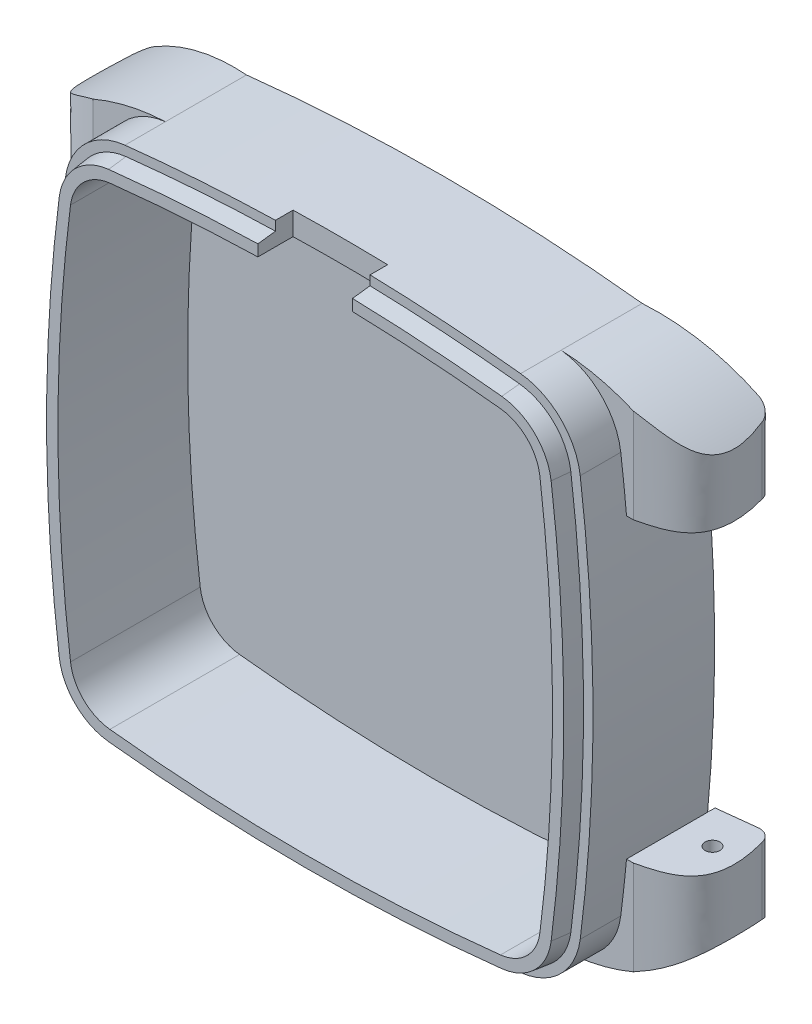
SolidWorks part; units mm, degrees
material "Özel Plastik"
ref_plane "Ön Düzlem" through (0, 0, 0) normal (0, 0, 1) x (1, 0, 0)
ref_plane "Üst Düzlem" through (0, 0, 0) normal (0, 1, 0) x (1, 0, 0)
ref_plane "Sağ Düzlem" through (0, 0, 0) normal (1, 0, 0) x (0, 0, -1)
sketch "Çizim1" plane through (0, 0, 0) normal (0, 0, 1) x (1, 0, 0)
  line L1 (-20, -20) -> (20, -20)
  line L2 (-20, -20) -> (-20, 20)
  line L3 (-20, 20) -> (20, 20)
  line L4 (20, -20) -> (20, 20)
  line L5 (-20, -20) -> (20, 20) construction
  line L6 (-20, 20) -> (20, -20) construction
  point P0 (0, 0)
  dimension "D1" = 40
  dimension "D2" = 40
extrude "Yükseklik-Ekstrüzyon1" add sketch "Çizim1" along normal mid plane 9 contours L3 L4 L1 L2
sketch "Çizim2" plane through (0, 0, 4.5) normal (0, 0, 1) x (1, 0, 0)
  line L0 (-20, 18.5) -> (20, 18.5) construction
  line L1 (-20, -20) -> (-20, 20) construction
  line L2 (20, -20) -> (20, 20) construction
  line L3 (-20, 20) -> (20, 20) construction
  line L4 (0, 0) -> (12.6557, 0) construction
  line L5 (-20, 20) -> (20, 20)
  line L6 (20, 20) -> (20, 18.5)
  line L7 (-20, 20) -> (-20, 18.5)
  line L8 (-20, -18.5) -> (20, -18.5) construction
  line L9 (-20, -20) -> (-20, -18.5)
  line L10 (20, -20) -> (20, -18.5)
  line L11 (-20, -20) -> (20, -20)
  arc A0 (-20, 18.5) -> (20, 18.5) centre (0, -114.0833) cw
  arc A1 (-20, -18.5) -> (20, -18.5) centre (0, 114.0833) ccw
  line M4 (-20, 20) -> (-20, -20)
  line M5 (-20, -20) -> (20, -20)
  line M6 (20, -20) -> (20, 20)
  line M7 (20, 20) -> (-20, 20)
  dimension "D1" = 1.5
extrude "Kes-Ekstrüzyon1" cut sketch "Çizim2" against normal through all contours A0 M7 M6 | A0 L5 M4 | A1 M4 M5 | A1 L11 M6 region at (-15.0056, 19.5504, 4.5) region at (15.0056, 19.5504, 4.5) region at (-15.0056, -19.5504, 4.5) region at (15.0056, -19.5504, 4.5)
sketch "Çizim3" plane through (0, 0, 4.5) normal (0, 0, 1) x (1, 0, 0)
  line L0 (18.5, 18.7176) -> (18.5, -18.7176) construction
  line L1 (20, -18.5) -> (20, 18.5) construction
  line L2 (20, 18.5) -> (20, -18.5)
  line L3 (0, 0) -> (0, -12.7146) construction
  line L4 (-18.5, 18.7176) -> (-18.5, -18.7176) construction
  line L5 (-20, 18.5) -> (-20, -18.5)
  arc A0 (20, 18.5) -> (-20, 18.5) centre (0, -114.0833) ccw construction
  arc A1 (-20, -18.5) -> (20, -18.5) centre (0, 114.0833) ccw construction
  arc A2 (18.5, 18.7176) -> (18.5, -18.7176) centre (-97.533, 0) cw
  arc A3 (18.5, -18.7176) -> (20, -18.5) centre (0, 114.0833) ccw
  arc A4 (20, 18.5) -> (18.5, 18.7176) centre (0, -114.0833) ccw
  arc A5 (-20, 18.5) -> (-18.5, 18.7176) centre (0, -114.0833) cw
  arc A6 (-18.5, -18.7176) -> (-20, -18.5) centre (0, 114.0833) cw
  arc A7 (-18.5, 18.7176) -> (-18.5, -18.7176) centre (97.533, 0) ccw
  arc M3 (-20, -18.5) -> (20, -18.5) centre (0, 114.0833) ccw
  line M4 (20, -18.5) -> (20, 18.5)
  arc M5 (20, 18.5) -> (-20, 18.5) centre (0, -114.0833) ccw
  line M6 (-20, 18.5) -> (-20, -18.5)
  dimension "D1" = 1.5
extrude "Kes-Ekstrüzyon2" cut sketch "Çizim3" against normal through all contours A2 L2 M5 | A2 M4 M3 | A7 L5 M3 | A7 M5 M6 region at (19.5513, 13.9634, 4.5) region at (19.5513, -13.9634, 4.5) region at (-19.5513, 13.9634, 4.5) region at (-19.5513, -13.9634, 4.5)
fillet "Radyus1" radius 5 4 edges at (-18.5, -18.7176, 0) (18.5, -18.7176, 0) (-18.5, 18.7176, 0) (18.5, 18.7176, 0)
shell "İç Boşaltma1" thickness 0.7 removed face at (0, 0, 4.5)
sketch "Çizim4" plane through (0, 0, -3.8) normal (0, 0, 1) x (1, 0, 0)
  arc A16 (-14.4573, -17.5082) -> (14.4573, -17.5082) centre (0, 114.0833) ccw
  arc A17 (14.4573, -17.5082) -> (17.3704, -14.6452) centre (14.0969, -14.2279) ccw
  arc A18 (17.3704, -14.6452) -> (17.3704, 14.6452) centre (-97.533, 0) ccw
  arc A19 (17.3704, 14.6452) -> (14.4573, 17.5082) centre (14.0969, 14.2279) ccw
  arc A20 (14.4573, 17.5082) -> (-14.4573, 17.5082) centre (0, -114.0833) ccw
  arc A21 (-14.4573, 17.5082) -> (-17.3704, 14.6452) centre (-14.0969, 14.2279) ccw
  arc A22 (-17.3704, 14.6452) -> (-17.3704, -14.6452) centre (97.533, 0) ccw
  arc A23 (-17.3704, -14.6452) -> (-14.4573, -17.5082) centre (-14.0969, -14.2279) ccw
  arc A24 (-14.4573, -17.5082) -> (14.4573, -17.5082) centre (0, 114.0833) ccw
  arc A25 (14.4573, -17.5082) -> (17.3704, -14.6452) centre (14.0969, -14.2279) ccw
  arc A26 (17.3704, -14.6452) -> (17.3704, 14.6452) centre (-97.533, 0) ccw
  arc A27 (17.3704, 14.6452) -> (14.4573, 17.5082) centre (14.0969, 14.2279) ccw
  arc A28 (14.4573, 17.5082) -> (-14.4573, 17.5082) centre (0, -114.0833) ccw
  arc A29 (-14.4573, 17.5082) -> (-17.3704, 14.6452) centre (-14.0969, 14.2279) ccw
  arc A30 (-17.3704, 14.6452) -> (-17.3704, -14.6452) centre (97.533, 0) ccw
  arc A31 (-17.3704, -14.6452) -> (-14.4573, -17.5082) centre (-14.0969, -14.2279) ccw
  arc A32 (-14.5665, -18.5022) -> (14.5665, -18.5022) centre (0, 114.0833) ccw
  arc A33 (14.5665, -18.5022) -> (18.3624, -14.7716) centre (14.0969, -14.2279) ccw
  arc A34 (18.3624, -14.7716) -> (18.3624, 14.7716) centre (-97.533, 0) ccw
  arc A35 (18.3624, 14.7716) -> (14.5665, 18.5022) centre (14.0969, 14.2279) ccw
  arc A36 (14.5665, 18.5022) -> (-14.5665, 18.5022) centre (0, -114.0833) ccw
  arc A37 (-14.5665, 18.5022) -> (-18.3624, 14.7716) centre (-14.0969, 14.2279) ccw
  arc A38 (-18.3624, 14.7716) -> (-18.3624, -14.7716) centre (97.533, 0) ccw
  arc A39 (-18.3624, -14.7716) -> (-14.5665, -18.5022) centre (-14.0969, -14.2279) ccw
  arc A40 (-14.5665, -18.5022) -> (14.5665, -18.5022) centre (0, 114.0833) ccw
  arc A41 (14.5665, -18.5022) -> (18.3624, -14.7716) centre (14.0969, -14.2279) ccw
  arc A42 (18.3624, -14.7716) -> (18.3624, 14.7716) centre (-97.533, 0) ccw
  arc A43 (18.3624, 14.7716) -> (14.5665, 18.5022) centre (14.0969, 14.2279) ccw
  arc A44 (14.5665, 18.5022) -> (-14.5665, 18.5022) centre (0, -114.0833) ccw
  arc A45 (-14.5665, 18.5022) -> (-18.3624, 14.7716) centre (-14.0969, 14.2279) ccw
  arc A46 (-18.3624, 14.7716) -> (-18.3624, -14.7716) centre (97.533, 0) ccw
  arc A47 (-18.3624, -14.7716) -> (-14.5665, -18.5022) centre (-14.0969, -14.2279) ccw
  dimension "D2" = 0
  dimension "D1" = 1
extrude "Yükseklik-Ekstrüzyon2" add sketch "Çizim4" along normal blind 9.6
sketch "Çizim7" plane through (0, 0, -4.5) normal (0, 0, -1) x (-1, 0, 0)
  line L0 (25.5, 14) -> (25.5, -14)
  line L1 (0, 0) -> (0, 12.7906) construction
  line L2 (0, 0) -> (-9.1265, 0) construction
  line L3 (-25.5, 14) -> (-25.5, -14)
  arc A0 (14.643, -19.198) -> (19.0568, -14.8601) centre (14.0969, -14.2279) ccw construction
  arc A1 (19.0568, -14.8601) -> (19.0568, 14.8601) centre (-97.533, 0) ccw construction
  arc A2 (19.0568, 14.8601) -> (14.643, 19.198) centre (14.0969, 14.2279) ccw construction
  arc A3 (14.643, -19.198) -> (19.0568, -14.8601) centre (14.0969, -14.2279) ccw
  arc A4 (19.0568, -14.8601) -> (19.0568, 14.8601) centre (-97.533, 0) ccw
  arc A5 (19.0568, 14.8601) -> (14.643, 19.198) centre (14.0969, 14.2279) ccw
  arc A6 (14.643, -19.198) -> (25.5, -14) centre (13.9336, -3.779) ccw
  arc A7 (14.643, 19.198) -> (25.5, 14) centre (13.9336, 3.779) cw
  arc A8 (-14.643, 19.198) -> (-25.5, 14) centre (-13.9336, 3.779) ccw
  arc A9 (-14.643, -19.198) -> (-25.5, -14) centre (-13.9336, -3.779) cw
  arc A10 (-19.0568, 14.8601) -> (-14.643, 19.198) centre (-14.0969, 14.2279) cw
  arc A11 (-19.0568, -14.8601) -> (-19.0568, 14.8601) centre (97.533, 0) cw
  arc A12 (-14.643, -19.198) -> (-19.0568, -14.8601) centre (-14.0969, -14.2279) cw
  point P5 (20, 0)
  dimension "D1" = 5.5
  dimension "D2" = 14
  dimension "D3" = 14
extrude "Yükseklik-Ekstrüzyon4" add sketch "Çizim7" against normal blind 6 and the other way blind 4
sketch "Çizim8" plane through (0, 0, 0) normal (0, 1, 0) x (1, 0, 0)
  line L0 (-14.643, 4.5) -> (-14.643, 8.5)
  line L1 (-27.9186, 10.7243) -> (-27.9186, -3)
  line L2 (-27.9186, -3) -> (-20, -1.5)
  line L3 (0, 4.5) -> (0, -13.103) construction
  line L4 (14.643, 4.5) -> (-14.643, 4.5) construction
  line L5 (27.9186, 10.7243) -> (14.643, 8.5)
  line L6 (22.4335, 5.3905) -> (14.643, 4.5)
  line L8 (27.9186, -3) -> (20, -1.5)
  line L9 (27.9186, 10.7243) -> (27.9186, -3)
  line L10 (-20, -1.5) -> (-19.0568, -1.5) construction
  line L13 (-22.4335, 5.3905) -> (-14.643, 4.5)
  line L14 (-25.5, -1.5) -> (-14.643, -1.5) construction
  line L15 (14.643, 4.5) -> (14.643, 8.5)
  line L18 (-27.9186, 10.7243) -> (-14.643, 8.5)
  arc A0 (-23.4243, 4.6022) -> (-22.4335, 5.3905) centre (-22.4469, 4.3906) cw
  arc A1 (23.4243, 4.6022) -> (22.4335, 5.3905) centre (22.4469, 4.3906) ccw
  spline S0 degree 3 poles (-20, -1.5) (-22.4731, -0.9161) (-24.7458, -0.1559) (-23.4243, 4.6022) knots 0 0 0 0 0.893244 0.893244 0.893244 0.893244
  spline S1 degree 3 poles (20, -1.5) (22.4731, -0.9161) (24.7458, -0.1559) (23.4243, 4.6022) knots 0 0 0 0 0.893244 0.893244 0.893244 0.893244
extrude "Kes-Ekstrüzyon4" cut sketch "Çizim8" against normal blind 38 and the other way blind 28
fillet "Radyus3" radius 0.2 6 edges at (20, 0, -4.5) (-20, 0, -4.5) (17.6017, 17.794, -4.5) (17.6017, -17.794, -4.5) (-17.6017, 17.794, -4.5) (-17.6017, -17.794, -4.5)
sketch "Çizim9" plane through (0, 0, 0) normal (0, 0, 1) x (1, 0, 0)
  line L0 (0, 0) -> (0, 33.3031) construction
  line L1 (-19.4841, 11) -> (-29.4841, 11)
  line L2 (29.4841, 11) -> (29.4841, -11)
  line L3 (-19.4841, -11) -> (-29.4841, -11)
  line L4 (-29.4841, 11) -> (-29.4841, -11)
  line L5 (19.4841, -11) -> (29.4841, -11)
  line L6 (19.4841, 11) -> (29.4841, 11)
  arc A0 (-14.643, -19.198) -> (14.643, -19.198) centre (0, 114.0833) ccw construction
  arc A2 (-19.0568, 14.8601) -> (-19.0568, -14.8601) centre (97.533, 0) ccw construction
  arc A3 (-19.4841, 11) -> (-19.4841, -11) centre (97.533, 0) ccw
  arc A4 (19.4841, 11) -> (19.4841, -11) centre (-97.533, 0) cw
  point P9 (0, -20)
  dimension "D1" = 9
  dimension "D2" = 10
  dimension "D5" = 22
extrude "Kes-Ekstrüzyon5" cut sketch "Çizim9" against normal blind 38 and the other way blind 38
sketch "Çizim12" plane through (0, 0, -4.5) normal (0, 0, -1) x (-1, 0, 0)
  line L0 (23.8131, -11) -> (20, -11) construction
  line L1 (-21.9066, 11) -> (20.7668, 11)
  line L2 (-21.9066, 11) -> (-21.9066, -11)
  line L3 (-21.9066, -11) -> (20.7668, -11)
  line L4 (20.7668, 11) -> (20.7668, -11)
  line L5 (-23.8131, 11) -> (-20, 11) construction
extrude "Kes-Ekstrüzyon9" cut sketch "Çizim12" along normal blind 10
sketch "Çizim13" plane through (0, 11, 0) normal (0, -1, 0) x (-1, 0, 0)
  line L5 (19.0568, -4.5) -> (20, -4.5) construction
  line L7 (19.4841, -1.5) -> (19.4841, 4.5) construction
  line L8 (-20, -4.5) -> (-19.0568, -4.5) construction
  line L9 (-19.4841, -1.5) -> (-19.4841, 4.5) construction
  circle A0 centre (-21.8441, 2.5) radius 0.55
  circle A1 centre (21.8441, 2.5) radius 0.55
  dimension "D1" = 1.1
  dimension "D4" = 1.1
  dimension "D2" = 7
  dimension "D3" = 2.36
  dimension "D5" = 7
  dimension "D6" = 2.36
extrude "Kes-Ekstrüzyon10" cut sketch "Çizim13" along normal blind 23.25 and the other way blind 1.25
chamfer "Pah1" distance 1.3 angle 7 8 edges at (-17.111, 17.2948, 5.8) (-19.3, 0, 5.8) (0, 19.3, 5.8) (-17.111, -17.2948, 5.8) (17.111, 17.2948, 5.8) (0, -19.3, 5.8) (19.3, 0, 5.8) (17.111, -17.2948, 5.8) first distance on face at (-16.7877, 16.9658, 5.15) first distance on face at (-18.8312, 0, 5.15) first distance on face at (0, 18.9011, 5.15) first distance on face at (-16.7877, -16.9658, 5.15) first distance on face at (16.7877, 16.9658, 5.15) first distance on face at (0, -18.9011, 5.15) first distance on face at (18.8312, 0, 5.15) first distance on face at (16.7877, -16.9658, 5.15)
sketch "Çizim14" plane through (0, 0, 0) normal (0, 1, 0) x (1, 0, 0)
  line L1 (3.5, -6.2) -> (-3.5, -6.2)
  line L2 (3.5, -6.2) -> (3.5, -3.2)
  line L3 (3.5, -3.2) -> (-3.5, -3.2)
  line L4 (-3.5, -6.2) -> (-3.5, -3.2)
  line L5 (-14.643, -4.5) -> (14.643, -4.5) construction
  line L6 (-14.4573, 3.8) -> (14.4573, 3.8) construction
  point P6 (0, -4.5)
  dimension "D1" = 3
  dimension "D2" = 7
  dimension "D3" = 3.5
  dimension "D4" = 7
extrude "Kes-Ekstrüzyon11" cut sketch "Çizim14" along normal blind 40
